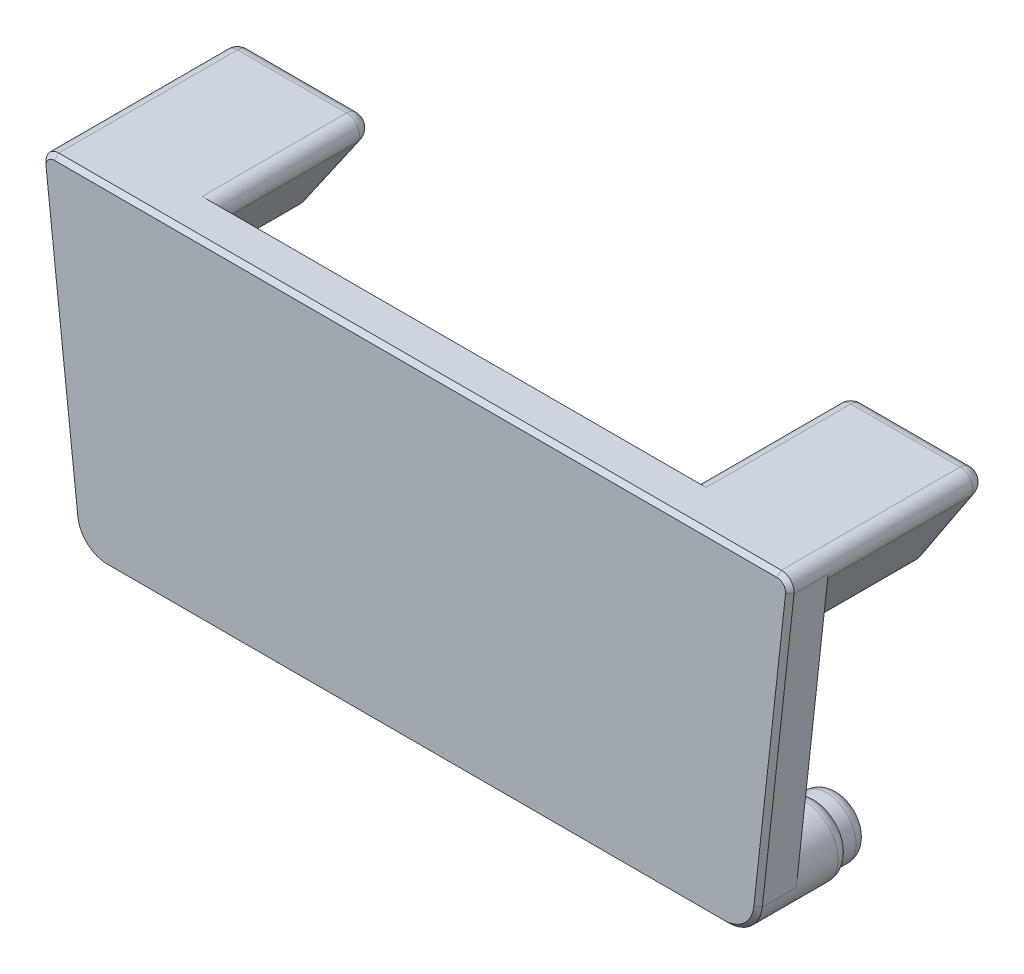
SolidWorks part; units mm, degrees
material "Thornel VCB-20 碳布"
ref_plane "前视基准面" through (0, 0, 0) normal (0, 0, 1) x (1, 0, 0)
ref_plane "上视基准面" through (0, 0, 0) normal (0, 1, 0) x (1, 0, 0)
ref_plane "右视基准面" through (0, 0, 0) normal (1, 0, 0) x (0, 0, -1)
sketch "草图1" plane through (0, 0, 0) normal (0, 0, 1) x (1, 0, 0)
  line L0 (166.7621, -253.6267) -> (179.2925, -234.6566) construction
  line L1 (176.7893, -230.0031) -> (151.1005, -230.0031) construction
  line L2 (148.6355, -234.713) -> (161.7939, -253.6831) construction
  line L3 (32.5995, -230.0031) -> (6.9107, -230.0031) construction
  line L4 (4.4075, -234.6566) -> (16.9379, -253.6267) construction
  line L5 (21.9061, -253.6831) -> (35.0645, -234.713) construction
  line L6 (166.7621, -253.6267) -> (179.2925, -234.6566)
  line L7 (176.7893, -230.0031) -> (151.1005, -230.0031)
  line L8 (148.6355, -234.713) -> (161.7939, -253.6831)
  line L9 (32.5995, -230.0031) -> (6.9107, -230.0031)
  line L10 (4.4075, -234.6566) -> (16.9379, -253.6267)
  line L11 (21.9061, -253.6831) -> (35.0645, -234.713)
  arc A0 (179.2925, -234.6566) -> (176.7893, -230.0031) centre (176.7893, -233.0031) ccw construction
  arc A1 (151.1005, -230.0031) -> (148.6355, -234.713) centre (151.1005, -233.0031) ccw construction
  arc A2 (161.7939, -253.6831) -> (166.7621, -253.6267) centre (164.2589, -251.9732) ccw construction
  arc A3 (6.9107, -230.0031) -> (4.4075, -234.6566) centre (6.9107, -233.0031) ccw construction
  arc A4 (16.9379, -253.6267) -> (21.9061, -253.6831) centre (19.4411, -251.9732) ccw construction
  arc A5 (35.0645, -234.713) -> (32.5995, -230.0031) centre (32.5995, -233.0031) ccw construction
  arc A6 (179.2925, -234.6566) -> (176.7893, -230.0031) centre (176.7893, -233.0031) ccw
  arc A7 (151.1005, -230.0031) -> (148.6355, -234.713) centre (151.1005, -233.0031) ccw
  arc A8 (161.7939, -253.6831) -> (166.7621, -253.6267) centre (164.2589, -251.9732) ccw
  arc A9 (6.9107, -230.0031) -> (4.4075, -234.6566) centre (6.9107, -233.0031) ccw
  arc A10 (16.9379, -253.6267) -> (21.9061, -253.6831) centre (19.4411, -251.9732) ccw
  arc A11 (35.0645, -234.713) -> (32.5995, -230.0031) centre (32.5995, -233.0031) ccw
extrude "凸台-拉伸1" add sketch "草图1" along normal up to surface (36 mm away)
sketch "草图2" plane through (0, 0, 19) normal (0, 0, 1) x (1, 0, 0)
  circle A0 centre (164.35, -300) radius 7 construction
  circle A1 centre (19.35, -300) radius 7 construction
  circle A2 centre (164.35, -300) radius 7
  circle A3 centre (19.35, -300) radius 7
extrude "凸台-拉伸2" add sketch "草图2" along normal up to surface (6 mm away) separate body
sketch "草图3" plane through (0, 0, 25) normal (0, 0, 1) x (1, 0, 0)
  circle A0 centre (164.35, -300) radius 8 construction
  circle A1 centre (19.35, -300) radius 8 construction
  circle A2 centre (164.35, -300) radius 8
  circle A3 centre (19.35, -300) radius 8
extrude "凸台-拉伸3" add sketch "草图3" along normal up to surface (11 mm away)
sketch "草图4" plane through (0, 0, 36) normal (0, 0, 1) x (1, 0, 0)
  line L1 (32.5995, -230.0031) -> (6.9107, -230.0031) construction
  line L5 (176.7893, -230.0031) -> (151.1005, -230.0031) construction
  line L7 (176.7893, -230.0031) -> (6.9107, -230.0031)
  line L11 (176.7893, -230.0031) -> (151.1005, -230.0031)
  line L12 (19.35, -308) -> (164.35, -308)
  line L13 (11.3985, -300.8793) -> (3.9289, -233.3329)
  line L14 (172.3015, -300.8793) -> (179.7711, -233.3329)
  arc A1 (6.9107, -230.0031) -> (4.4075, -234.6566) centre (6.9107, -233.0031) ccw construction
  arc A4 (179.2925, -234.6566) -> (176.7893, -230.0031) centre (176.7893, -233.0031) ccw construction
  circle A6 centre (164.35, -300) radius 8 construction
  circle A7 centre (19.35, -300) radius 8 construction
  arc A9 (6.9107, -230.0031) -> (3.9289, -233.3329) centre (6.9107, -233.0031) ccw
  arc A12 (179.7711, -233.3329) -> (176.7893, -230.0031) centre (176.7893, -233.0031) ccw
  arc A14 (164.35, -308) -> (172.3015, -300.8793) centre (164.35, -300) ccw
  arc A15 (11.3985, -300.8793) -> (19.35, -308) centre (19.35, -300) ccw
  circle M9 centre (19.35, -300) radius 8
extrude "凸台-拉伸4" add sketch "草图4" along normal blind 10 contours L12 A14 L14 A12 L7 A9 L13 M9 | A9 M9 region at (92.9824, -267.7913, 36) region at (19.35, -300, 36)
fillet "圆角1" radius 3 16 edges at (171.35, -300, 19) (26.35, -300, 19) (19.7551, -230.0031, 0) (4.2687, -231.5819, 0) (10.6727, -244.1416, 0) (19.4071, -254.973, 0) (28.4853, -244.198, 0) (35.2575, -231.612, 0) (173.0273, -244.1416, 0) (179.4313, -231.5819, 0) (163.9449, -230.0031, 0) (148.4425, -231.612, 0) (155.2147, -244.198, 0) (164.2929, -254.973, 0) (27.35, -300, 25) (172.35, -300, 25)
chamfer "倒角1" distance 1 angle 45 12 edges at (91.85, -308, 46) (169.6869, -305.9596, 46) (14.0131, -305.9596, 46) (176.0363, -267.1061, 46) (7.6637, -267.1061, 46) (179.0241, -231.0018, 46) (4.6759, -231.0018, 46) (91.85, -230.0031, 46) (91.85, -230.0031, 36) (176.0363, -267.1061, 36) (91.85, -308, 36) (7.6637, -267.1061, 36)
